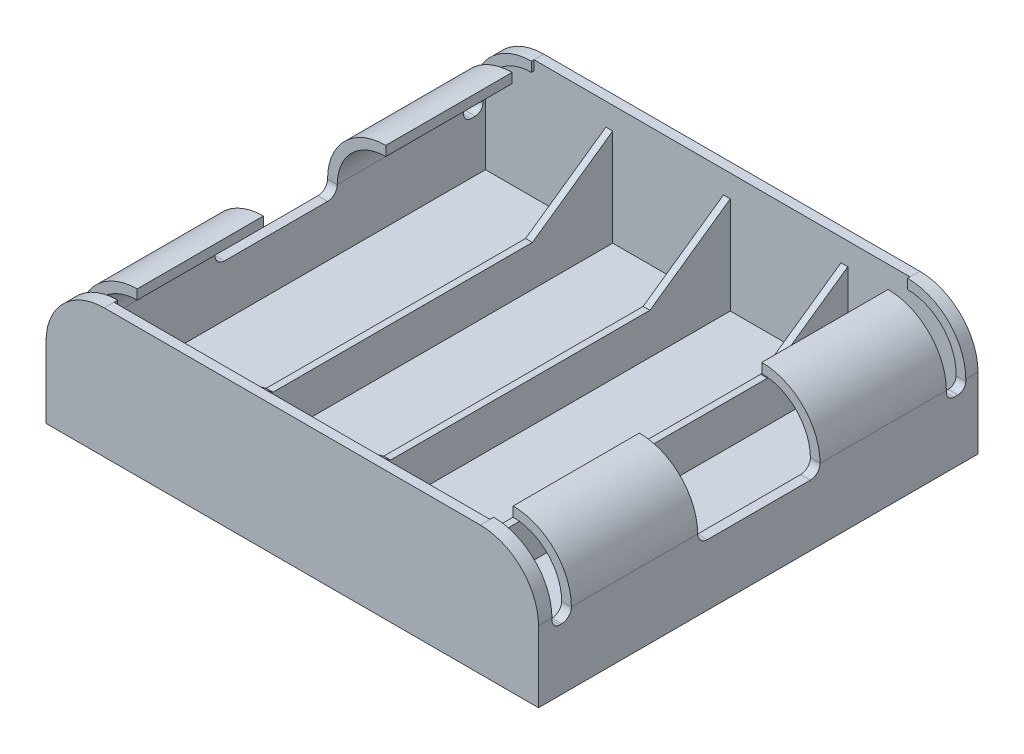
SolidWorks part; units mm, degrees
ref_plane "Front" through (0, 0, 0) normal (0, 0, 1) x (1, 0, 0)
ref_plane "Top" through (0, 0, 0) normal (0, 1, 0) x (1, 0, 0)
ref_plane "Right" through (0, 0, 0) normal (1, 0, 0) x (0, 0, -1)
sketch "Sketch1" plane through (0, 0, 0) normal (0, 0, 1) x (1, 0, 0)
  line L1 (-73.505, 34.812) -> (-9.116, 34.812)
  line L2 (-73.505, 34.812) -> (-73.505, 17.921)
  line L3 (-73.505, 17.921) -> (-9.116, 17.921)
  line L4 (-9.116, 34.812) -> (-9.116, 17.921)
  dimension "D1" = 64.389
  dimension "D2" = 16.891
extrude "Extrude1" add sketch "Sketch1" along normal blind 57.4548
fillet "Fillet2" radius 7.62 2 edges at (-73.505, 34.812, 28.7274) (-9.116, 34.812, 28.7274)
shell "Shell1" thickness 1.27 removed face at (-41.3105, 34.812, 28.7274)
sketch "Sketch2" plane through (0, 0, 0) normal (1, 0, 0) x (0, 0, -1)
  line L0 (-58.293, 34.812) -> (-55.6987, 34.812)
  line L1 (-57.4548, 34.812) -> (0, 34.812) construction
  line L2 (-55.6987, 34.812) -> (-55.6987, 26.938)
  line L3 (-54.6827, 25.922) -> (-54.4287, 25.922)
  line L4 (-53.1587, 27.192) -> (-53.1587, 34.812)
  line L5 (-53.1587, 34.812) -> (-36.6487, 34.812)
  line L6 (-36.6487, 34.812) -> (-36.6487, 27.192)
  line L7 (-35.3787, 25.922) -> (-21.9167, 25.922)
  line L8 (-20.6467, 27.192) -> (-20.6467, 34.812)
  line L9 (-20.6467, 34.812) -> (-4.1367, 34.812)
  line L10 (-4.1367, 34.812) -> (-4.1367, 26.938)
  line L11 (-3.1207, 25.922) -> (-2.6127, 25.922)
  line L12 (-57.4548, 17.921) -> (0, 17.921) construction
  line L13 (-1.5967, 26.938) -> (-1.5967, 34.812)
  line L14 (-1.5967, 34.812) -> (0, 34.812)
  arc A0 (-35.3787, 25.922) -> (-36.6487, 27.192) centre (-35.3787, 27.192) cw
  arc A1 (-20.6467, 27.192) -> (-21.9167, 25.922) centre (-21.9167, 27.192) cw
  arc A2 (-54.4287, 25.922) -> (-53.1587, 27.192) centre (-54.4287, 27.192) ccw
  arc A3 (-55.6987, 26.938) -> (-54.6827, 25.922) centre (-54.6827, 26.938) ccw
  arc A4 (-4.1367, 26.938) -> (-3.1207, 25.922) centre (-3.1207, 26.938) ccw
  arc A5 (-1.5967, 26.938) -> (-2.6127, 25.922) centre (-2.6127, 26.938) cw
  point P20 (-36.6487, 25.922)
  point P24 (-20.6467, 25.922)
  point P27 (-53.1587, 25.922)
  point P30 (-55.6987, 25.922)
  point P32 (-4.1367, 25.922)
  point P35 (-1.5967, 25.922)
  dimension "D6" = 1.27
  dimension "D7" = 1.27
  dimension "D8" = 1.016
  dimension "D9" = 1.016
  dimension "D10" = 8.001
  dimension "D1" = 16.002
  dimension "D2" = 16.51
  dimension "D3" = 16.51
  dimension "D4" = 2.54
  dimension "D5" = 2.54
  dimension "D11" = 8.001
  dimension "D12" = 8.001
extrude "Cut-Extrude1" cut sketch "Sketch2" against normal through all and the other way through all
sketch "Sketch4" plane through (0, 19.191, 0) normal (0, 1, 0) x (-1, 0, 0)
  line L0 (72.235, 1.27) -> (10.386, 1.27) construction
  line L1 (40.231, 1.27) -> (41.12, 1.27)
  line L2 (40.231, 1.27) -> (40.231, 56.1848)
  line L3 (40.231, 56.1848) -> (41.12, 56.1848)
  line L4 (41.12, 1.27) -> (41.12, 56.1848)
  line L5 (72.235, 56.1848) -> (10.386, 56.1848) construction
  line L6 (16.736, 1.27) -> (65.885, 1.27) construction
  line L7 (24.864, 1.27) -> (25.753, 1.27)
  line L8 (24.864, 1.27) -> (24.864, 56.1848)
  line L9 (24.864, 56.1848) -> (25.753, 56.1848)
  line L10 (25.753, 1.27) -> (25.753, 56.1848)
  line L11 (16.736, 56.1848) -> (65.885, 56.1848) construction
  line L12 (10.386, 56.1848) -> (10.386, 1.27) construction
  line L13 (55.598, 1.27) -> (56.487, 1.27)
  line L14 (55.598, 1.27) -> (55.598, 56.1848)
  line L15 (55.598, 56.1848) -> (56.487, 56.1848)
  line L16 (56.487, 1.27) -> (56.487, 56.1848)
  dimension "D1" = 0.889
  dimension "D2" = 0.889
  dimension "D3" = 14.478
  dimension "D4" = 14.478
extrude "Extrude2" add sketch "Sketch4" along normal blind 12.7
sketch "Sketch5" plane through (-41.12, 0, 0) normal (-1, 0, 0) x (0, 0, 1)
  line L0 (1.27, 31.891) -> (11.7729, 24.525)
  line L1 (11.7729, 24.525) -> (45.6819, 24.525)
  line L2 (45.6819, 24.525) -> (56.1848, 31.891)
  line L3 (1.27, 31.891) -> (56.1848, 31.891) construction
  line L4 (56.1848, 31.891) -> (56.1848, 19.191) construction
  line L6 (1.27, 19.191) -> (56.1848, 19.191) construction
  line L7 (1.27, 31.891) -> (56.1848, 31.891)
  dimension "D1" = 5.334
  dimension "D2" = 33.909
extrude "Cut-Extrude2" cut sketch "Sketch5" against normal blind 19.05 and the other way blind 20.32
